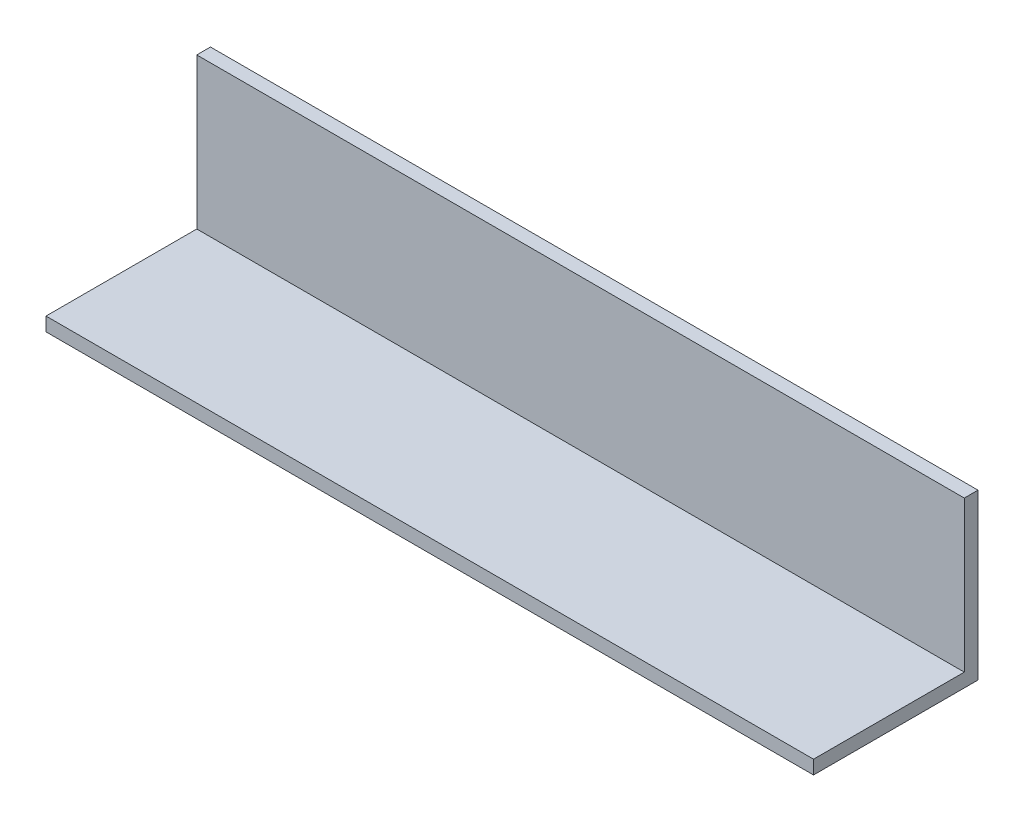
SolidWorks part; units mm, degrees
ref_plane "Front Plane" through (0, 0, 0) normal (0, 0, 1) x (1, 0, 0)
ref_plane "Top Plane" through (0, 0, 0) normal (0, 1, 0) x (1, 0, 0)
ref_plane "Right Plane" through (0, 0, 0) normal (1, 0, 0) x (0, 0, -1)
sketch "Sketch2" plane through (0, 0, 0) normal (1, 0, 0) x (0, 0, -1)
  line L1 (0, 0) -> (76.2, 0)
  line L2 (0, 0) -> (0, 76.2)
  line L3 (0, 76.2) -> (76.2, 76.2)
  line L4 (76.2, 0) -> (76.2, 76.2)
  line L5 (0, 76.2) -> (69.85, 76.2)
  line L6 (0, 76.2) -> (0, 6.35)
  line L7 (0, 6.35) -> (69.85, 6.35)
  line L8 (69.85, 76.2) -> (69.85, 6.35)
  dimension "D1" = 76.2
  dimension "D2" = 76.2
  dimension "D3" = 6.35
  dimension "D4" = 6.35
extrude "Boss-Extrude2" add sketch "Sketch2" along normal blind 355.6 contours L3 L8 L7 L2 L1 L4 region at (0, 3.175, -1.0776)
